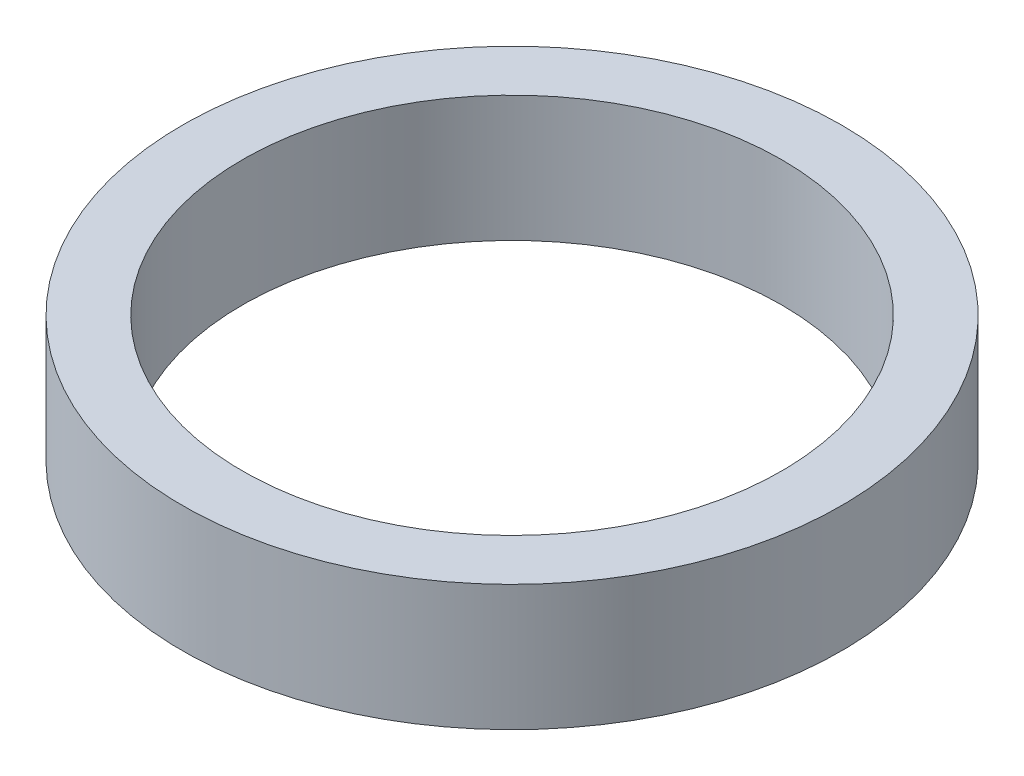
SolidWorks part; units mm, degrees
ref_plane "Front Plane" through (0, 0, 0) normal (0, 0, 1) x (1, 0, 0)
ref_plane "Top Plane" through (0, 0, 0) normal (0, 1, 0) x (1, 0, 0)
ref_plane "Right Plane" through (0, 0, 0) normal (1, 0, 0) x (0, 0, -1)
sketch "Sketch1" plane through (0, 0, 0) normal (0, 1, 0) x (1, 0, 0)
  circle A0 centre (0, 0) radius 55
  dimension "FLANGE_OD" = 110
extrude "Boss-Extrude1" add sketch "Sketch1" along normal blind 21
sketch "Sketch2" plane through (0, 0, 0) normal (0, 1, 0) x (1, 0, 0)
  circle A0 centre (0, 0) radius 45
  dimension "BORE_D" = 90
extrude "Cut-Extrude1" cut sketch "Sketch2" along normal through all
sketch "Sketch3" plane through (0, 21, 0) normal (0, 1, 0) x (1, 0, 0)
  circle A0 centre (0, 0) radius 23.8201 construction
  circle A1 centre (-23.8201, 0) radius 1.6068
  dimension "BOLT_D" = 3.2137
  dimension "BOLT_PCD" = 47.6402
extrude "Cut-Extrude2" cut sketch "Sketch3" against normal blind 20.9035 rebuild error yes
pattern_circular "CirPattern1" count 8 over 360 rebuild error yes
